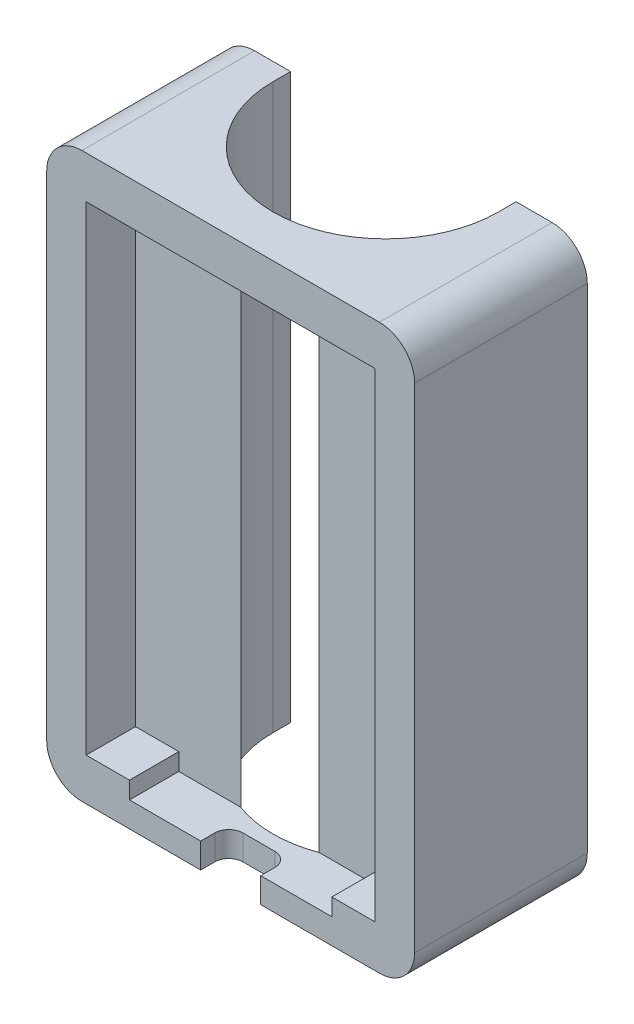
SolidWorks part; units mm, degrees
ref_plane "Plan de face" through (0, 0, 0) normal (0, 0, 1) x (1, 0, 0)
ref_plane "Plan de dessus" through (0, 0, 0) normal (0, 1, 0) x (1, 0, 0)
ref_plane "Plan de droite" through (0, 0, 0) normal (1, 0, 0) x (0, 0, -1)
sketch "Esquisse1" plane through (0, 0, 0) normal (0, 0, 1) x (1, 0, 0)
  line L1 (-41.2248, -2.0065) -> (10.9752, -2.0065)
  line L2 (-41.2248, -2.0065) -> (-41.2248, -82.0065)
  line L3 (-41.2248, -82.0065) -> (10.9752, -82.0065)
  line L4 (10.9752, -2.0065) -> (10.9752, -82.0065)
extrude "Boss.-Extru.2" add sketch "Esquisse1" along normal blind 22
sketch "Esquisse2" plane through (0, -82.0065, 0) normal (0, -1, 0) x (1, 0, 0)
  line L0 (-41.2248, 0) -> (10.9752, 0) construction
  circle A0 centre (-15.1248, 0) radius 16
sketch "Esquisse3" plane through (0, 0, 22) normal (0, 0, 1) x (1, 0, 0)
  line L0 (-41.2248, -2.0065) -> (-41.2248, -82.0065) construction
  line L1 (-39.4848, -5.5677) -> (9.2352, -5.5677)
  line L2 (-39.4848, -5.5677) -> (-39.4848, -78.4453)
  line L3 (-39.4848, -78.4453) -> (9.2352, -78.4453)
  line L4 (9.2352, -5.5677) -> (9.2352, -78.4453)
  line L5 (10.9752, -82.0065) -> (10.9752, -2.0065) construction
  line L6 (10.9752, -2.0065) -> (-41.2248, -2.0065) construction
  line L7 (-31.1248, -82.0065) -> (0.8752, -82.0065) construction
  dimension "D1" = 1.74
  dimension "D2" = 1.74
  dimension "D3" = 3.5612
  dimension "D4" = 3.5612
extrude "Enlèv. mat.-Extru.1" cut sketch "Esquisse3" against normal blind 5
fillet "Congé1" radius 10 4 edges at (-39.4848, -78.4453, 19.5) (9.2352, -78.4453, 19.5) (9.2352, -5.5677, 19.5) (-39.4848, -5.5677, 19.5)
sketch "Esquisse5" plane through (0, 0, 17) normal (0, 0, 1) x (1, 0, 0)
  line L0 (-35.6248, -42.0065) -> (5.3752, -42.0065) construction
  line L1 (-35.6248, -8.0065) -> (5.3752, -8.0065)
  line L2 (-35.6248, -8.0065) -> (-35.6248, -15.5677)
  line L3 (-35.6248, -76.0065) -> (-29.4848, -76.0065)
  line L4 (5.3752, -8.0065) -> (5.3752, -15.5677)
  line L5 (10.9752, -2.0065) -> (-41.2248, -2.0065) construction
  line L6 (5.3752, -68.4453) -> (5.3752, -76.0065)
  line L7 (-0.7648, -76.0065) -> (5.3752, -76.0065)
  line L8 (-29.4848, -8.0065) -> (-0.7648, -8.0065)
  line L9 (10.9752, -82.0065) -> (10.9752, -2.0065) construction
  line L10 (-35.6248, -68.4453) -> (-35.6248, -15.5677)
  line L11 (5.3752, -15.5677) -> (5.3752, -68.4453)
  line L13 (-35.6248, -15.5677) -> (-35.6248, -8.0065)
  line L15 (-29.4848, -8.0065) -> (-35.6248, -8.0065)
  line L16 (-39.4848, -15.5677) -> (-39.4848, -5.5677)
  line L17 (-39.4848, -5.5677) -> (-29.4848, -5.5677)
  line L18 (-15.1248, -8.0065) -> (-15.1248, -76.0065) construction
  line L26 (9.2352, -15.5677) -> (9.2352, -5.5677)
  line L27 (9.2352, -5.5677) -> (-0.7648, -5.5677)
  line L29 (9.2352, -68.4453) -> (9.2352, -78.4453)
  line L30 (9.2352, -78.4453) -> (-0.7648, -78.4453)
  line L31 (-0.7648, -78.4453) -> (-0.7648, -76.0065)
  line L33 (-29.4848, -78.4453) -> (-29.4848, -76.0065)
  line L34 (-39.4848, -78.4453) -> (-29.4848, -78.4453)
  line L35 (-39.4848, -68.4453) -> (-39.4848, -78.4453)
  line L36 (-35.6248, -68.4453) -> (-35.6248, -76.0065)
  line M5 (-39.4848, -15.5677) -> (-39.4848, -68.4453)
  arc M6 (-39.4848, -68.4453) -> (-29.4848, -78.4453) centre (-29.4848, -68.4453) ccw
  arc M8 (-0.7648, -78.4453) -> (9.2352, -68.4453) centre (-0.7648, -68.4453) ccw
  line M9 (9.2352, -68.4453) -> (9.2352, -15.5677)
  arc M10 (9.2352, -15.5677) -> (-0.7648, -5.5677) centre (-0.7648, -15.5677) ccw
  line M11 (-0.7648, -5.5677) -> (-29.4848, -5.5677)
  arc M12 (-29.4848, -5.5677) -> (-39.4848, -15.5677) centre (-29.4848, -15.5677) ccw
  dimension "D1" = 41
  dimension "D2" = 68
  dimension "D3" = 6
  dimension "D4" = 5.6
extrude "Boss.-Extru.4" add sketch "Esquisse5" along normal blind 5 contours L36 L10 L2 L1 L4 L11 L6 L7 L31 L33 L3 M8 M9 M10 M11 M12 M5 M6 region at (-36.5014, -11.7871, 17)
extrude "Enlèv. mat.-Extru.3" cut sketch "Esquisse2" against normal through all contours A0
sketch "Esquisse7" plane through (0, 0, 17) normal (0, 0, 1) x (1, 0, 0)
  line L0 (-35.6248, -8.0065) -> (5.3752, -8.0065)
  line L1 (5.3752, -8.0065) -> (5.3752, -76.0065)
  line L2 (5.3752, -76.0065) -> (-0.7648, -76.0065)
  line L3 (-0.7648, -76.0065) -> (-0.7648, -78.4453)
  line L4 (-0.7648, -78.4453) -> (-29.4848, -78.4453)
  line L5 (-29.4848, -78.4453) -> (-29.4848, -76.0065)
  line L6 (-29.4848, -76.0065) -> (-35.6248, -76.0065)
  line L7 (-35.6248, -76.0065) -> (-35.6248, -8.0065)
extrude "Enlèv. mat.-Extru.5" cut sketch "Esquisse7" against normal blind 2
sketch "Esquisse8" plane through (0, 0, 22) normal (0, 0, 1) x (1, 0, 0)
  line L1 (-19.3798, -78.4453) -> (-10.8698, -78.4453)
  line L2 (-19.3798, -78.4453) -> (-19.3798, -82.0065)
  line L3 (-19.3798, -82.0065) -> (-10.8698, -82.0065)
  line L4 (-10.8698, -78.4453) -> (-10.8698, -82.0065)
  line L7 (-0.7648, -78.4453) -> (-0.7648, -76.0065) construction
  line L8 (-29.4848, -76.0065) -> (-29.4848, -78.4453) construction
  dimension "D1" = 10.105
  dimension "D2" = 10.105
extrude "Enlèv. mat.-Extru.6" cut sketch "Esquisse8" against normal blind 4
fillet "Congé3" radius 2 2 edges at (-10.8698, -80.2259, 18) (-19.3798, -80.2259, 18)
sketch "Esquisse9" plane through (0, 0, 0) normal (0, 0, -1) x (-1, 0, 0)
  line L1 (31.1248, -2.0065) -> (41.2248, -2.0065)
  line L2 (31.1248, -2.0065) -> (31.1248, -82.0065)
  line L3 (31.1248, -82.0065) -> (41.2248, -82.0065)
  line L4 (41.2248, -2.0065) -> (41.2248, -82.0065)
  line L5 (-10.9752, -2.0065) -> (-0.8752, -2.0065)
  line L6 (-10.9752, -2.0065) -> (-10.9752, -82.0065)
  line L7 (-10.9752, -82.0065) -> (-0.8752, -82.0065)
  line L8 (-0.8752, -2.0065) -> (-0.8752, -82.0065)
extrude "Boss.-Extru.5" add sketch "Esquisse9" along normal blind 2.5
fillet "Congé4" radius 5 4 edges at (10.9752, -2.0065, 9.75) (10.9752, -82.0065, 9.75) (-41.2248, -82.0065, 9.75) (-41.2248, -2.0065, 9.75)
